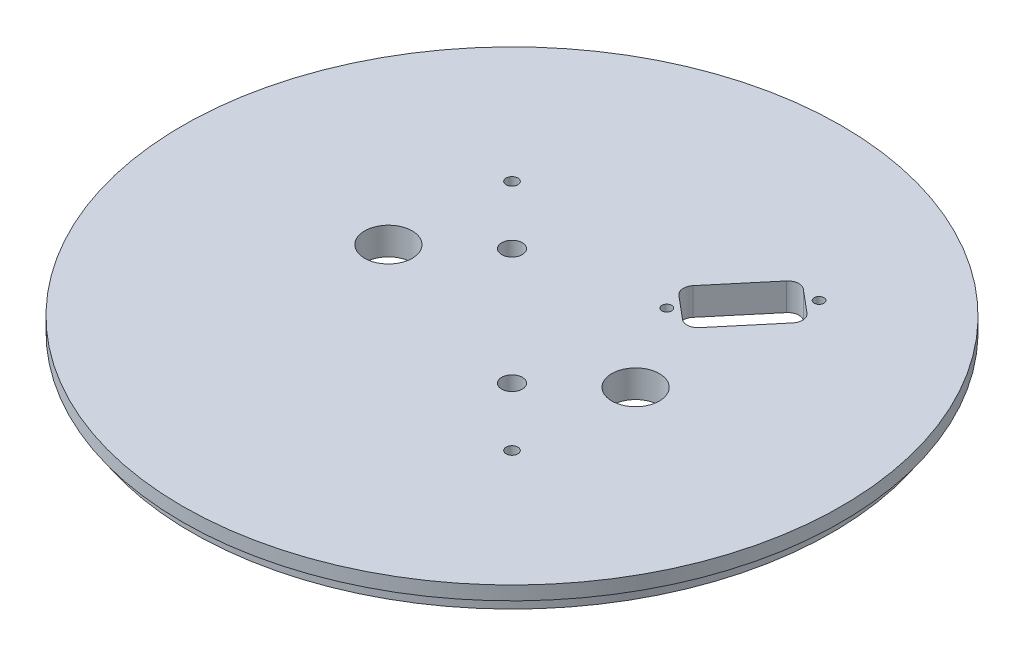
SolidWorks part; units mm, degrees
material "6061-T6 (SS)"
ref_plane "Front Plane" through (0, 0, 0) normal (0, 0, 1) x (1, 0, 0)
ref_plane "Top Plane" through (0, 0, 0) normal (0, 1, 0) x (1, 0, 0)
ref_plane "Right Plane" through (0, 0, 0) normal (1, 0, 0) x (0, 0, -1)
sketch "Sketch1" plane through (0, 0, 0) normal (0, 1, 0) x (1, 0, 0)
  line L0 (0, -76.2) -> (0, 76.2) construction
  line L1 (-76.2, 0) -> (76.2, 0) construction
  line L2 (-26.9408, 26.9408) -> (0, 0) construction
  line L3 (0, 56.7387) -> (0, 29.6936) construction
  line L4 (3.6407, 56.7387) -> (3.6407, 29.6936) construction
  line L5 (-3.6407, 56.7387) -> (-3.6407, 29.6936) construction
  line L6 (0, -56.7387) -> (0, -29.6936) construction
  line L7 (3.6407, -56.7387) -> (3.6407, -29.6936) construction
  line L8 (-3.6407, -56.7387) -> (-3.6407, -29.6936) construction
  line L9 (-53.8815, -53.8815) -> (54.3236, 54.3236) construction
  circle A0 centre (0, 0) radius 76.2
  circle A1 centre (0, 0) radius 3.175 construction
  circle A2 centre (28.575, 0) radius 5.5
  circle A3 centre (-28.575, 0) radius 5.5
  circle A4 centre (-26.9408, 26.9408) radius 1.3589
  arc A6 (3.6407, 56.7387) -> (-3.6407, 56.7387) centre (0, 56.7387) ccw construction
  arc A7 (-3.6407, 29.6936) -> (3.6407, 29.6936) centre (0, 29.6936) ccw construction
  arc A8 (3.6407, -56.7387) -> (-3.6407, -56.7387) centre (0, -56.7387) cw construction
  arc A9 (-3.6407, -29.6936) -> (3.6407, -29.6936) centre (0, -29.6936) cw construction
  circle A10 centre (26.9408, -26.9408) radius 1.3589
  circle A11 centre (-13.4704, 13.4704) radius 2.3813
  circle A12 centre (13.4704, -13.4704) radius 2.3813
  point P16 (0, 43.2162)
  point P19 (0, 0)
  point P26 (0, -43.2162)
  dimension "D1" = 152.4
  dimension "D2" = 6.35
  dimension "D3" = 11
  dimension "D5" = 2.7178
  dimension "D8" = 4.7625
  dimension "D6" = 38.1
  dimension "D7" = 45
  dimension "D4" = 45
  dimension "D9" = 28.575
extrude "Boss-Extrude1" add sketch "Sketch1" along normal blind 6.35
sketch "Sketch2" plane through (0, 0, 0) normal (0, -1, 0) x (1, 0, 0)
  circle A0 centre (0, 0) radius 76.2
  circle A1 centre (0, 0) radius 74.041
  dimension "D1" = 152.4
  dimension "D2" = 148.082
extrude "Cut-Extrude1" cut sketch "Sketch2" against normal blind 3.175
sketch "Sketch3" plane through (0, 6.35, 0) normal (0, 1, 0) x (1, 0, 0)
  line L0 (0, 76.2) -> (0, -76.2) construction
  line L1 (-76.2, 0) -> (76.2, 0) construction
  line L2 (0, 34.798) -> (0, 13.97) construction
  line L3 (3.2385, 34.798) -> (3.2385, 13.97)
  line L4 (-3.2385, 34.798) -> (-3.2385, 13.97)
  line L5 (0, -34.798) -> (0, -13.97) construction
  line L6 (3.2385, -34.798) -> (3.2385, -13.97)
  line L7 (-3.2385, -34.798) -> (-3.2385, -13.97)
  circle A0 centre (0, 0) radius 76.2 construction
  arc A1 (3.2385, 34.798) -> (-3.2385, 34.798) centre (0, 34.798) ccw
  arc A2 (-3.2385, 13.97) -> (3.2385, 13.97) centre (0, 13.97) ccw
  arc A3 (3.2385, -34.798) -> (-3.2385, -34.798) centre (0, -34.798) cw
  arc A4 (-3.2385, -13.97) -> (3.2385, -13.97) centre (0, -13.97) cw
  point P7 (0, 13.97)
  point P8 (0, 34.798)
  point P12 (0, 24.384)
  point P20 (0, -24.384)
  point P25 (0, -34.798)
  point P26 (0, -13.97)
  dimension "D1" = 13.97
  dimension "D2" = 20.828
  dimension "D3" = 6.477
extrude "Cut-Extrude2" cut sketch "Sketch3" against normal blind 3.556 from offset 5.969 offset against normal yes
hole_wizard "Tap Drill for #4-40 Tap1" positions "Sketch5" profile "Sketch6" hole size "#4-40" standard "ANSI Inch" end condition through all
sketch "Sketch5" plane through (0, 6.35, 0) normal (0, 1, 0) x (1, 0, 0)
  line L0 (0, 0) -> (53.6567, 63.9455) construction
  line L2 (0, 0) -> (28.575, 0) construction
  point P0 (16.3268, 19.4575)
  point P2 (32.3965, 38.6086)
  point P16 (21.0794, 29.0602)
  point P17 (22.6266, 26.9653)
  point P18 (7.5803, 9.0339)
  dimension "D1" = 50
  dimension "D2" = 25
  dimension "D3" = 25.4
sketch "Sketch6" plane through (16.3268, 6.35, -19.4575) normal (1, 0, 0) x (0, 0, 1)
  line L0 (0, 0) -> (0, 6.35)
  line L1 (0, 6.35) -> (1.1303, 6.35)
  line L2 (1.1303, 6.35) -> (1.1303, 0)
  line L5 (1.1303, 0) -> (0, 0)
  line L11 (0, -6.35) -> (0, 107.95) construction
  dimension "Thru Hole Dia." = 2.2606
  dimension "Thru Hole Depth" = 6.35
sketch "Sketch4" plane through (0, 6.35, 0) normal (0, 1, 0) x (1, 0, 0)
  line L0 (15.1695, 23.4128) -> (20.423, 19.0046)
  line L1 (14.8564, 26.9913) -> (24.7219, 38.7485)
  line L2 (24.0014, 19.3177) -> (33.8669, 31.0749)
  line L3 (28.3003, 39.0616) -> (33.5538, 34.6533)
  line L4 (0, 0) -> (32.3965, 38.6086) construction
  circle A1 centre (16.3268, 19.4575) radius 1.1303 construction
  arc A2 (24.7219, 38.7485) -> (28.3003, 39.0616) centre (26.6676, 37.1158) cw
  arc A3 (33.8669, 31.0749) -> (33.5538, 34.6533) centre (31.9212, 32.7076) ccw
  arc A4 (20.423, 19.0046) -> (24.0014, 19.3177) centre (22.0557, 20.9503) ccw
  arc A5 (14.8564, 26.9913) -> (15.1695, 23.4128) centre (16.8021, 25.3586) ccw
  point P8 (36.7686, 31.9558)
  point P11 (17.7962, 21.2087)
  dimension "D4" = 2.54
  dimension "D1" = 2.286
  dimension "D2" = 2.286
  dimension "D3" = 11.938
extrude "Cut-Extrude3" cut sketch "Sketch4" against normal through all
equation "\"leadDist\"=1.5"
equation "\"Lead_Screw_Dist\" = 2.25in"
equation "\"D9@Sketch1\"=\"Lead_Screw_Dist\"/2"
equation "\"Lead_Screw_Diam\" = 11mm"
equation "\"D3@Sketch1\"=\"Lead_Screw_Diam\""
equation "\"Bodytube_OD\" = 6.17in"
equation "\"Bodytube_ID\" = 5.998in"
equation "\"Motor_OD\" = 4in"
equation "\"Fwd_Tube_Length\" = 40in"
equation "\"Mid_Tube_Length\" = 1in"
equation "\"Aft_Section_Length\"= 39in"
equation "\"AB_Coupler_OD_Length\"= 1in"
equation "\"AB_Coupling_Section_Length\"= 0.375in"
equation "\"AB_Coupler_Length\"= \"AB_Coupler_OD_Length\" + \"AB_Coupling_Section_Length\" * 2"
equation "\"Cutout_Angle\" = 80"
equation "\"AB_Paddle_Height\" = 0.375in"
equation "\"AB_Coupler_Num_Screws\"= 6"
equation "\"Num_Cutouts\" = 3"
equation "\"AB_Coupler_OD\"= 6.17in"
equation "\"AB_Coupler_ID\"= 5.75in"
equation "\"AB_Coupler_Surface_Diameter\"= 5.998in"
equation "\"AB_Coupling_Screw_Diameter\"= 0.1065in"
equation "\"AB_Central_Bushing_Length\" = .75in"
equation "\"Lead_Screw_Length\" = (\"Mid_Coupler_Length\" + 2*0.375in + 2*0.5in)"
equation "\"Paddle_Pin_Offset\" = .25in"
equation "\"Paddle_Pin_Radius\" = 2.25in"
equation "\"SS_Paddle_Pin_Radius\" = 2.25*0.66in"
equation "\"Paddle_Gear_OD\" = 3.2in"
equation "\"Drive_Gear_OD\" = 1.7in"
equation "\"Fwd_BKHD_From_Top\" = 18in"
equation "\"Fin_Thickness\"= .118in"
equation "\"Guiderail_Cutout_Diameter\"= 1.5in"
equation "\"DB9_Hole_Dist\" = 25mm"
equation "\"Airbrakes_Wire_Hole_Dia\" = .25in"
equation "\"Airbrakes_Wire_Hole_Dist\" = 1.1in"
equation "\"Servo_Gear_Offset\" = 0.5in"
equation "\"Mid_Coupler_Length\" = 13in"
equation "\"D2@Sketch5\"=\"DB9_Hole_Dist\""
equation "\"DB9_Relief_Width\" = 0.47in"
equation "\"DB9_Relief_Hole_Offset\" = 0.09in"
equation "\"D1@Sketch4\"=\"DB9_Relief_Hole_Offset\""
equation "\"D2@Sketch4\"=\"DB9_Relief_Hole_Offset\""
equation "\"D3@Sketch4\"=\"DB9_Relief_Width\""
